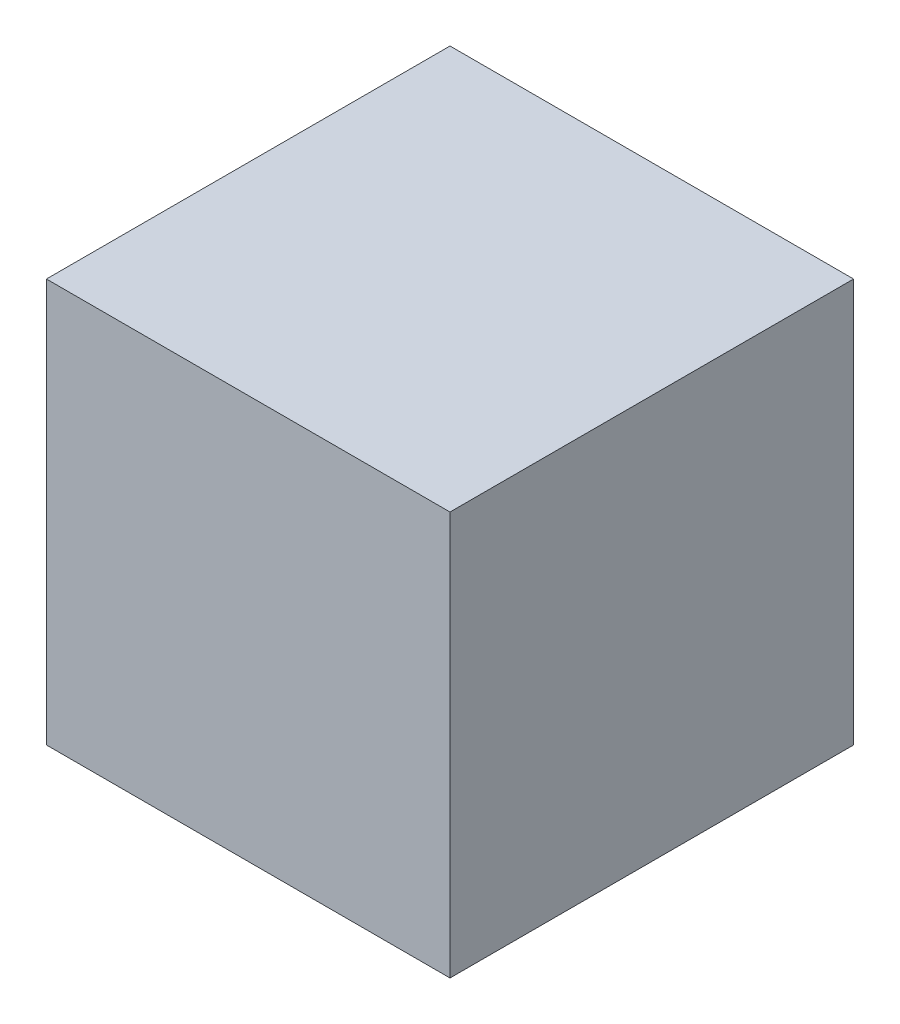
SolidWorks part; units mm, degrees
material "ABS"
ref_plane "Front Plane" through (0, 0, 0) normal (0, 0, 1) x (1, 0, 0)
ref_plane "Top Plane" through (0, 0, 0) normal (0, 1, 0) x (1, 0, 0)
ref_plane "Right Plane" through (0, 0, 0) normal (1, 0, 0) x (0, 0, -1)
sketch "Sketch1" plane through (0, 0, 0) normal (0, 0, 1) x (1, 0, 0)
  line L1 (0, 0) -> (1, 0)
  line L2 (0, 0) -> (0, 1)
  line L3 (0, 1) -> (1, 1)
  line L4 (1, 0) -> (1, 1)
  dimension "D1" = 1
  dimension "D2" = 1
extrude "Boss-Extrude1" add sketch "Sketch1" along normal blind 1
